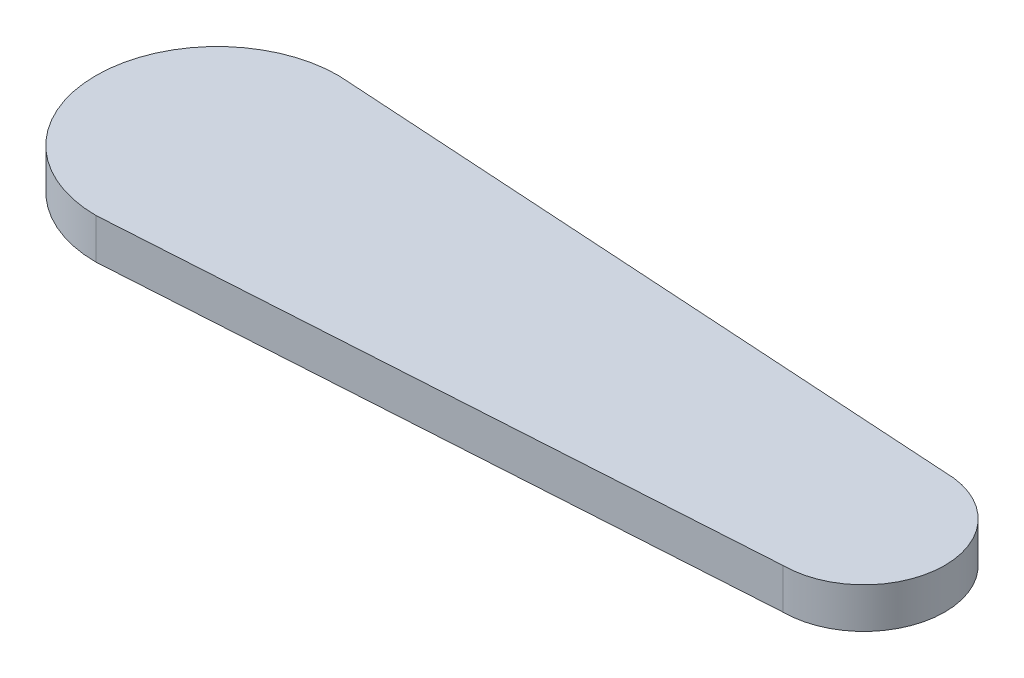
SolidWorks part; units mm, degrees
ref_plane "Front Plane" through (0, 0, 0) normal (0, 0, 1) x (1, 0, 0)
ref_plane "Top Plane" through (0, 0, 0) normal (0, 1, 0) x (1, 0, 0)
ref_plane "Right Plane" through (0, 0, 0) normal (1, 0, 0) x (0, 0, -1)
sketch "Sketch1" plane through (0, 0, 0) normal (0, 1, 0) x (1, 0, 0)
  line L0 (0, 15) -> (80, 10)
  line L1 (0, -15) -> (80, -10)
  line L2 (3.3, 7.5597) -> (3.3, 4.2597)
  line L3 (7.1, -5.9403) -> (7.1, -2.0903)
  line L4 (-11.6947, 2.2971) -> (3.3, 4.2597)
  line L5 (-11.6947, -0.6776) -> (3.3, -2.6403)
  line L6 (20.0621, 2.301) -> (7.1, 3.7097)
  line L7 (20.0621, -0.6815) -> (7.1, -2.0903)
  line L8 (7.1, 3.7097) -> (7.1, 7.5597)
  line L9 (3.3, -2.6403) -> (3.3, -5.9403)
  line L10 (5.2, 7.5597) -> (5.2, -5.9403) construction
  line L11 (-11.5, 0.8097) -> (19.9, 0.8097) construction
  arc A0 (0, 15) -> (0, -15) centre (0, 0) ccw
  arc A1 (80, -10) -> (80, 10) centre (80, 0) ccw
  arc A4 (-11.6947, 2.2971) -> (-11.6947, -0.6776) centre (-11.5, 0.8097) ccw
  arc A5 (20.0621, -0.6815) -> (20.0621, 2.301) centre (19.9, 0.8097) ccw
  arc A6 (3.3, -5.9403) -> (7.1, -5.9403) centre (5.2, -5.9403) ccw
  arc A7 (7.1, 7.5597) -> (3.3, 7.5597) centre (5.2, 7.5597) ccw
  circle A8 centre (5.2, 0.8097) radius 1.275
  circle A9 centre (5.2, 0.8097) radius 2.35
  circle A10 centre (19.9, 0.8097) radius 0.5
  circle A11 centre (5.2, 7.5597) radius 0.5
  circle A12 centre (-11.5, 0.8097) radius 0.5
  circle A13 centre (5.2, -5.9403) radius 0.5
  circle A14 centre (5.2, -3.9403) radius 0.5
  circle A15 centre (5.2, 5.5597) radius 0.5
  circle A16 centre (-9.5, 0.8097) radius 0.5
  circle A17 centre (-7.5, 0.8097) radius 0.5
  circle A18 centre (-5.5, 0.8097) radius 0.5
  circle A19 centre (-3.5, 0.8097) radius 0.5
  circle A20 centre (-1.5, 0.8097) radius 0.5
  circle A21 centre (0.5, 0.8097) radius 0.5
  circle A22 centre (17.9, 0.8097) radius 0.5
  circle A23 centre (15.9, 0.8097) radius 0.5
  circle A24 centre (13.9, 0.8097) radius 0.5
  circle A25 centre (11.9, 0.8097) radius 0.5
  circle A26 centre (9.9, 0.8097) radius 0.5
  point P12 (21.4, 0.8097)
  point P15 (-13, 0.8097)
  point P28 (-15, 0)
  dimension "D1" = 30
  dimension "D2" = 20
  dimension "D5" = 2.55
  dimension "D6" = 4.7
  dimension "D7" = 1
  dimension "D8" = 2
  dimension "D3" = 80
  dimension "D4" = 2
  dimension "D9" = 7
  dimension "D10" = 6
extrude "Boss-Extrude1" add sketch "Sketch1" along normal blind 5 contours L0 A1 L1 A0
extrude "Cut-Extrude1" cut sketch "Sketch1<3>" along normal blind 1.5 contours L6 L8 A7 L2 L4 A4 L5 L9 A6 L3 L7 A5
sketch "Sketch1<3>" plane through (0, 0, 0) normal (0, 1, 0) x (1, 0, 0) same geometry as "Sketch1"
